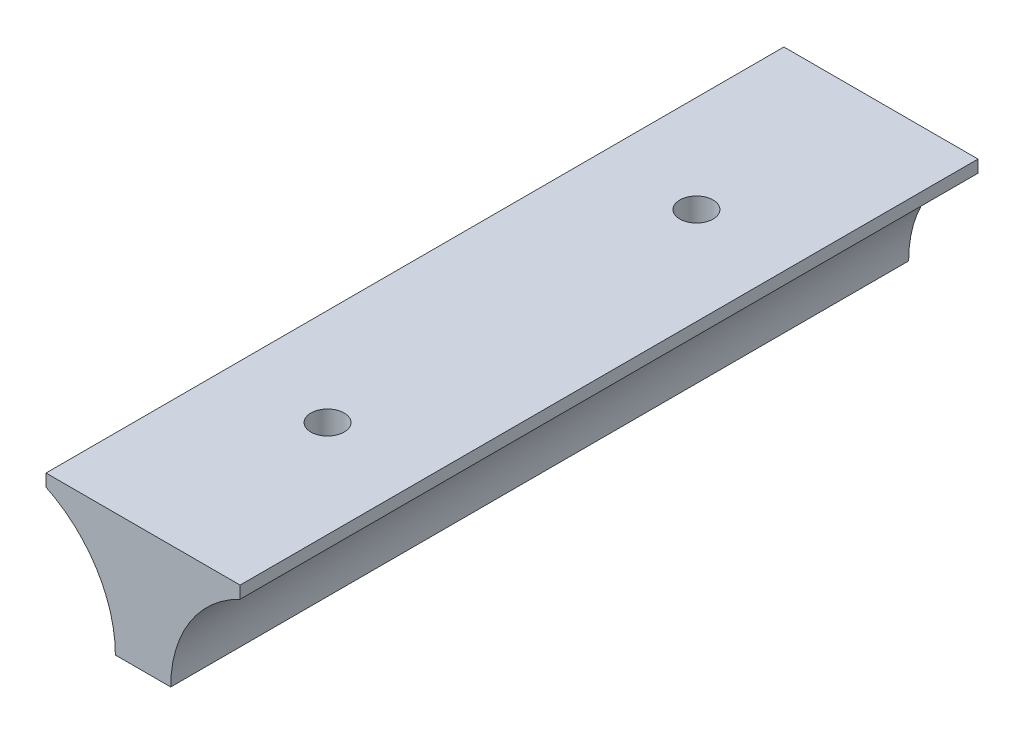
SolidWorks part; units mm, degrees
ref_plane "Front" through (0, 0, 0) normal (0, 0, 1) x (1, 0, 0)
ref_plane "Top" through (0, 0, 0) normal (0, 1, 0) x (1, 0, 0)
ref_plane "Right" through (0, 0, 0) normal (1, 0, 0) x (0, 0, -1)
sketch "Sketch1" plane through (0, 0, 0) normal (0, 0, 1) x (1, 0, 0)
  line L0 (-2.25, 0) -> (2.25, 0)
  line L1 (7.8911, 9) -> (7.8911, 10)
  line L2 (7.8911, 10) -> (-7.8911, 10)
  line L3 (-7.8911, 10) -> (-7.8911, 9)
  arc A0 (2.25, 0) -> (7.8911, 9) centre (12.25, 0) cw
  arc A1 (-2.25, 0) -> (-7.8911, 9) centre (-12.25, 0) ccw
  point P9 (0, 0)
  point P10 (0, 10)
  dimension "D1" = 10
  dimension "D2" = 10
  dimension "D3" = 4.5
  dimension "D4" = 1
extrude "Boss-Extrude1" add sketch "Sketch1" along normal blind 60
sketch "Sketch2" plane through (0, 10, 0) normal (0, 1, 0) x (1, 0, 0)
  line L0 (0, -60) -> (0, 0) construction
  line L1 (7.8911, -60) -> (-7.8911, -60) construction
  line L2 (7.8911, 0) -> (-7.8911, 0) construction
  point P6 (0, -45)
  point P7 (0, -15)
  dimension "D1" = 15
  dimension "D2" = 15
hole_wizard "Ø2.7 (2.7) Diameter Hole1" positions "3DSketch1" profile "Sketch3" hole size "Ø2.7" standard "ANSI Metric" end condition up to next
sketch3d "3DSketch1"
  point P0 (0, 10, 45)
  point P3 (0, 10, 15)
sketch "Sketch3" plane through (0, 10, 45) normal (1, 0, 0) x (0, 0, 1)
  line L0 (0, 0) -> (0, 10)
  line L1 (0, 10) -> (1.35, 10)
  line L2 (1.35, 10) -> (1.35, 0)
  line L5 (1.35, 0) -> (0, 0)
  line L11 (0, -6.35) -> (0, 107.95) construction
  dimension "Thru Hole Dia." = 2.7
  dimension "Thru Hole Depth" = 10
